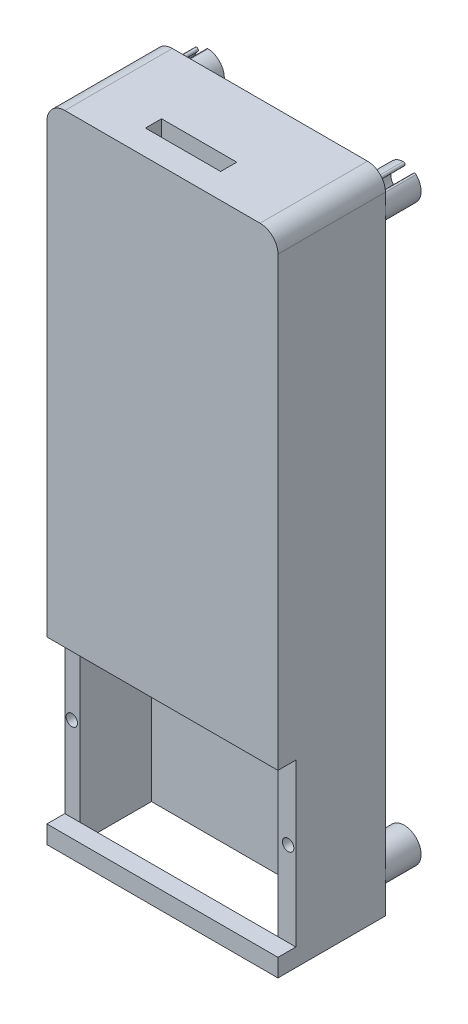
SolidWorks part; units mm, degrees
ref_plane "Alzado" through (0, 0, 0) normal (0, 0, 1) x (1, 0, 0)
ref_plane "Planta" through (0, 0, 0) normal (0, 1, 0) x (1, 0, 0)
ref_plane "Vista lateral" through (0, 0, 0) normal (1, 0, 0) x (0, 0, -1)
sketch "Croquis1" plane through (0, 0, 0) normal (0, 0, 1) x (1, 0, 0)
  line L1 (-32.25, -90) -> (32.25, -90)
  line L2 (-32.25, -90) -> (-32.25, 90)
  line L3 (-32.25, 90) -> (32.25, 90)
  line L4 (32.25, -90) -> (32.25, 90)
  line L5 (-32.25, -90) -> (32.25, 90) construction
  line L6 (-32.25, 90) -> (32.25, -90) construction
  point P0 (0, 0)
  dimension "D1" = 180
  dimension "D2" = 64.5
extrude "Saliente-Extruir1" add sketch "Croquis1" along normal blind 30
sketch "Croquis2" plane through (0, -90, 0) normal (0, -1, 0) x (1, 0, 0)
  line L5 (-28.06, 5) -> (27.25, 5)
  line L6 (27.25, 5) -> (27.25, 25)
  line L7 (0, 0) -> (0, 25.0059) construction
  line L10 (-32.25, 0) -> (32.25, 0) construction
  line L13 (27.25, 25) -> (-28.06, 25)
  line L14 (-28.06, 25) -> (-28.06, 5)
  line L16 (-32.25, 30) -> (32.25, 30) construction
  line L17 (32.25, 30) -> (32.25, 0) construction
  point P0 (0, 11.4401)
  dimension "D1" = 5
  dimension "D2" = 5
  dimension "D3" = 5
  dimension "D4" = 55.31
  dimension "D5" = 20
extrude "Cortar-Extruir1" cut sketch "Croquis2" against normal blind 155
sketch "Croquis3" plane through (0, 0, 0) normal (0, 0, -1) x (-1, 0, 0)
  line L0 (-32.25, 90) -> (-27.25, 90)
  line L1 (-27.25, 90) -> (27.25, 90)
  line L2 (-32.25, 85) -> (-32.25, -85)
  line L3 (-27.25, -90) -> (27.25, -90)
  line L4 (32.25, 85) -> (32.25, -85)
  line L5 (-32.25, 85) -> (-32.25, 90)
  line L6 (27.25, 90) -> (32.25, 90)
  line L7 (32.25, 90) -> (32.25, 85)
  line L8 (32.25, -85) -> (32.25, -90)
  line L9 (32.25, -90) -> (27.25, -90)
  line L10 (-32.25, -85) -> (-32.25, -90)
  line L11 (-32.25, -90) -> (-27.25, -90)
  arc A0 (-32.25, -85) -> (-27.25, -90) centre (-27.25, -85) ccw
  arc A1 (27.25, -90) -> (32.25, -85) centre (27.25, -85) ccw
  arc A2 (-27.25, 90) -> (-32.25, 85) centre (-27.25, 85) ccw
  arc A3 (27.25, 90) -> (32.25, 85) centre (27.25, 85) cw
  point P10 (32.25, -90)
  point P13 (-32.25, 90)
  line M9 (-32.25, 90) -> (-32.25, -90)
  line M11 (32.25, -90) -> (32.25, 90)
  line M12 (32.25, 90) -> (-32.25, 90)
  dimension "D1" = 5
extrude "Cortar-Extruir2" cut sketch "Croquis3" against normal blind 155 contours A2 M12 M9 region at (31.1332, 88.8832, 0)
ref_plane "Plano1" through (27.25, 90, 0) normal (1, 0, 0) x (0, 0, -1)
extrude "Cortar-Extruir4" cut sketch "Croquis3<4>" against normal blind 155 contours A3 M12 M11 region at (-31.1332, 88.8832, 0)
sketch "Croquis3<4>" plane through (0, 0, 0) normal (0, 0, -1) x (-1, 0, 0) same geometry as "Croquis3"
sketch "Croquis9" plane through (0, 0, 30) normal (0, 0, 1) x (1, 0, 0)
  line L0 (0, -90) -> (0, 0) construction
  line L1 (-32.25, -90) -> (32.25, -90) construction
  line L3 (-32.25, -85) -> (32.25, -85)
  line L4 (-32.25, -85) -> (-32.25, -39.8)
  line L5 (-32.25, -39.8) -> (32.25, -39.8)
  line L6 (32.25, -85) -> (32.25, -39.8)
  line L7 (-32.25, -85) -> (32.25, -39.8) construction
  line L8 (-32.25, -39.8) -> (32.25, -85) construction
  line L10 (-32.25, -90) -> (-32.25, 90) construction
  point P5 (0, -62.4)
  dimension "D1" = 5
  dimension "D2" = 0
  dimension "D3" = 45.2
sketch "Croquis12" plane through (0, -90, 0) normal (0, -1, 0) x (-1, 0, 0)
  line L0 (32.25, -15) -> (-32.25, -15) construction
  line L1 (32.25, -30) -> (32.25, 0) construction
  line L2 (-32.25, -30) -> (-32.25, 0) construction
  line L3 (30.155, 0) -> (30.155, -30) construction
  line L4 (32.25, 0) -> (-32.25, 0) construction
  line L5 (32.25, -30) -> (-32.25, -30) construction
  line L6 (28.06, -25) -> (28.06, -5) construction
  line L7 (-30.15, 0) -> (-30.15, -30) construction
  circle A0 centre (30.1834, -15) radius 1.6
  circle A1 centre (-30.15, -15) radius 1.6
  dimension "D1" = 3.2
  dimension "D2" = 3.2
  dimension "D3" = 2.095
  dimension "D4" = 4.19
  dimension "D5" = 2.1
extrude "Cortar-Extruir8" cut sketch "Croquis12" against normal blind 10
sketch "Croquis14" plane through (0, 0, 0) normal (0, 0, -1) x (-1, 0, 0)
  line L0 (-27.25, 91.9445) -> (-27.25, 88.0555) construction
  line L1 (0, 90) -> (0, -90) construction
  line L2 (32.25, 90) -> (-32.25, 90) construction
  line L3 (-32.25, 0) -> (32.25, 0) construction
  line L4 (-32.25, -90) -> (-32.25, 90) construction
  line L5 (32.25, -90) -> (32.25, 90) construction
  arc A0 (-27.25, 84.4073) -> (-30.4578, 83.1831) centre (-27.4722, 80.1742) cw construction
  arc A1 (-30.8109, 83.5389) -> (-27.2237, 84.9078) centre (-27.4722, 80.1742) ccw
  arc A2 (-30.1048, 82.8273) -> (-27.2763, 83.9067) centre (-27.4722, 80.1742) ccw
  arc A3 (-30.1048, 82.8273) -> (-30.8109, 83.5389) centre (-30.4578, 83.1831) ccw
  arc A4 (-27.2237, 84.9078) -> (-27.2763, 83.9067) centre (-27.25, 84.4073) ccw
  arc A5 (27.25, 84.4073) -> (30.4578, 83.1831) centre (27.4722, 80.1742) ccw construction
  arc A6 (30.8109, 83.5389) -> (27.2237, 84.9078) centre (27.4722, 80.1742) cw
  arc A7 (30.1048, 82.8273) -> (27.2763, 83.9067) centre (27.4722, 80.1742) cw
  arc A8 (30.1048, 82.8273) -> (30.8109, 83.5389) centre (30.4578, 83.1831) cw
  arc A9 (27.2237, 84.9078) -> (27.2763, 83.9067) centre (27.25, 84.4073) cw
  arc A10 (27.25, -84.4073) -> (30.4578, -83.1831) centre (27.4722, -80.1742) cw construction
  arc A11 (30.8109, -83.5389) -> (27.2237, -84.9078) centre (27.4722, -80.1742) ccw
  arc A12 (30.1048, -82.8273) -> (27.2763, -83.9067) centre (27.4722, -80.1742) ccw
  arc A13 (30.1048, -82.8273) -> (30.8109, -83.5389) centre (30.4578, -83.1831) ccw
  arc A14 (27.2237, -84.9078) -> (27.2763, -83.9067) centre (27.25, -84.4073) ccw
  arc A15 (-27.25, -84.4073) -> (-30.4578, -83.1831) centre (-27.4722, -80.1742) ccw construction
  arc A16 (-30.8109, -83.5389) -> (-27.2237, -84.9078) centre (-27.4722, -80.1742) cw
  arc A17 (-30.1048, -82.8273) -> (-27.2763, -83.9067) centre (-27.4722, -80.1742) cw
  arc A18 (-30.1048, -82.8273) -> (-30.8109, -83.5389) centre (-30.4578, -83.1831) cw
  arc A19 (-27.2237, -84.9078) -> (-27.2763, -83.9067) centre (-27.25, -84.4073) cw
  point P3 (-25.9609, 76.2139)
  point P18 (25.9609, 76.2139)
  point P32 (25.9609, -76.2139)
  point P40 (-25.9609, -76.2139)
extrude "Saliente-Extruir2" add sketch "Croquis14" along normal blind 10
extrude "Cortar-Extruir10" cut sketch "Croquis9" against normal blind 5
sketch "Croquis15" plane through (0, 0, 25) normal (0, 0, 1) x (1, 0, 0)
  line L0 (-30.155, -39.8) -> (-30.4583, -85) construction
  line L1 (-28.06, -39.8) -> (-32.25, -39.8) construction
  line L2 (-32.25, -90) -> (32.25, 90) construction
  line L3 (-32.25, -85) -> (32.25, -85) construction
  line L4 (29.75, -39.8) -> (30.4583, -85) construction
  line L5 (32.25, -39.8) -> (27.25, -39.8) construction
  line L6 (-32.25, 90) -> (32.25, -90) construction
  line L8 (32.25, -61.4) -> (-32.25, -61.4) construction
  line L9 (32.25, -90) -> (32.25, 90) construction
  line L10 (-32.25, -90) -> (-32.25, 90) construction
  circle A0 centre (30.0885, -61.4) radius 1.6
  circle A1 centre (-30.2999, -61.4) radius 1.6
  dimension "D1" = 3.2
  dimension "D2" = 3.2
  dimension "D3" = 23.6
extrude "Cortar-Extruir11" cut sketch "Croquis15" against normal blind 10
sketch "Croquis18" plane through (0, 90, 0) normal (0, 1, 0) x (1, 0, 0)
  line L0 (27.25, 0) -> (27.25, -30) construction
  line L1 (-11.75, -18.5) -> (9.25, -18.5)
  line L2 (-11.75, -18.5) -> (-11.75, -23)
  line L3 (-11.75, -23) -> (9.25, -23)
  line L4 (9.25, -18.5) -> (9.25, -23)
  line L5 (-32.25, 0) -> (32.25, 0) construction
  line L6 (27.25, -1.9445) -> (27.25, 1.9445) construction
  line L7 (-27.25, 0) -> (-27.25, -30) construction
  line L8 (-32.25, 0) -> (-32.25, -30) construction
  line L9 (-27.25, -5) -> (27.25, -5) construction
  line L10 (-32.25, 0) -> (32.25, 0) construction
  dimension "D1" = 5
  dimension "D2" = 5
  dimension "D3" = 18
  dimension "D4" = 15.5
  dimension "D5" = 21
  dimension "D6" = 13.5
  dimension "D7" = 18
  dimension "D8" = 4.5
extrude "Cortar-Extruir12" cut sketch "Croquis18" against normal up to next
